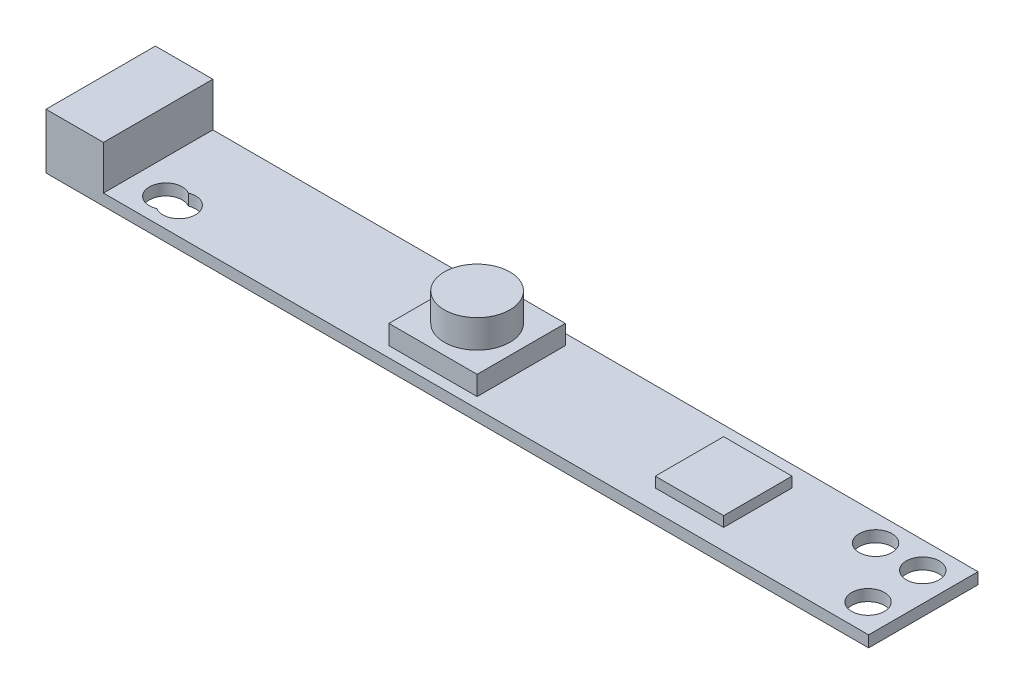
SolidWorks part; units mm, degrees
ref_plane "Front Plane" through (0, 0, 0) normal (0, 0, 1) x (1, 0, 0)
ref_plane "Top Plane" through (0, 0, 0) normal (0, 1, 0) x (1, 0, 0)
ref_plane "Right Plane" through (0, 0, 0) normal (1, 0, 0) x (0, 0, -1)
sketch "Sketch1" plane through (0, 0, 0) normal (0, 1, 0) x (1, 0, 0)
  line L1 (-30.075, -4) -> (30.075, -4)
  line L2 (-30.075, -4) -> (-30.075, 4)
  line L3 (-30.075, 4) -> (30.075, 4)
  line L4 (30.075, -4) -> (30.075, 4)
  line L5 (-30.075, -4) -> (30.075, 4) construction
  line L6 (-30.075, 4) -> (30.075, -4) construction
  point P0 (0, 0)
  dimension "D1" = 60.15
  dimension "D2" = 8
extrude "Boss-Extrude1" add sketch "Sketch1" along normal blind 0.83
sketch "Sketch2" plane through (0, 0.83, 0) normal (0, 1, 0) x (1, 0, 0)
  line L0 (-30.075, 4) -> (-30.075, -4) construction
  line L1 (-5.775, 3.225) -> (0.675, 3.225)
  line L2 (-5.775, 3.225) -> (-5.775, -3.225)
  line L3 (-5.775, -3.225) -> (0.675, -3.225)
  line L4 (0.675, 3.225) -> (0.675, -3.225)
  line L5 (-5.775, 3.225) -> (0.675, -3.225) construction
  line L6 (-5.775, -3.225) -> (0.675, 3.225) construction
  line L7 (30.075, -4) -> (30.075, 4) construction
  circle A0 centre (-2.55, 0) radius 2.4
  point P6 (0, 0)
  dimension "D4" = 4.8
  dimension "D1" = 6.45
  dimension "D2" = 30.75
  dimension "D3" = 35.85
extrude "Boss-Extrude2" add sketch "Sketch2" along normal offset from surface (1.41 mm away) 2.24 contours A0 | L4 L1 L2 L3 A0 region at (-2.55, 0.83, -3.1338) region at (-2.55, 0.83, 0) up to face at (0, 0, 0)
extrude "Boss-Extrude3" add sketch "Sketch2<3>" along normal offset from surface (3.47 mm away) 4.3 contours A0 region at (-2.55, 0.83, 0) up to face at (0, 0, 0)
sketch "Sketch2<3>" plane through (0, 0.83, 0) normal (0, 1, 0) x (1, 0, 0) same geometry as "Sketch2"
sketch "Sketch3" plane through (0, 0.83, 0) normal (0, 1, 0) x (1, 0, 0)
  line L0 (-30.075, -4) -> (30.075, -4) construction
  line L1 (-30.075, 4) -> (-25.875, 4)
  line L2 (-30.075, 4) -> (-30.075, -4)
  line L3 (-30.075, -4) -> (-25.875, -4)
  line L4 (-25.875, 4) -> (-25.875, -4)
  dimension "D1" = 4.2
extrude "Boss-Extrude4" add sketch "Sketch3" along normal offset from surface (3.21 mm away) 4.04 up to face at (0, 0, 0)
hole_wizard "M2 Clearance Hole1" positions "Sketch4" profile "Sketch5" hole size "M2" standard "ISO" end condition up to next
sketch "Sketch4" plane through (0, 0.83, 0) normal (0, 1, 0) x (1, 0, 0)
  line L0 (30.075, -4) -> (30.075, 4) construction
  line L1 (30.075, 4) -> (-25.875, 4) construction
  line L2 (-25.875, -4) -> (30.075, -4) construction
  line L3 (-30.075, -4) -> (-30.075, 4) construction
  point P0 (24.52, 2.065)
  point P2 (27.97, 2.065)
  point P4 (27.97, -1.935)
  point P6 (-23.39, -1.925)
  point P8 (-22.33, -2.005)
  point P11 (0, 0)
  point P12 (0, 0)
  point P19 (0, 0)
  dimension "D1" = 2.105
  dimension "D2" = 1.935
  dimension "D3" = 5.555
  dimension "D4" = 2.065
  dimension "D5" = 1.995
  dimension "D6" = 2.075
  dimension "D7" = 6.685
  dimension "D8" = 52.405
sketch "Sketch5" plane through (24.52, 0.83, -2.065) normal (1, 0, 0) x (0, 0, 1)
  line L0 (0, 0) -> (0, 0.83)
  line L1 (0, 0.83) -> (1.2, 0.83)
  line L2 (1.2, 0.83) -> (1.2, 0)
  line L5 (1.2, 0) -> (0, 0)
  line L11 (0, -6.35) -> (0, 107.95) construction
  dimension "Thru Hole Dia." = 2.4
  dimension "Thru Hole Depth" = 0.83
ref_plane "Plane1" through (-2.55, 0, 0) normal (1, 0, 0) x (0, 0, -1)
sketch "Sketch6" plane through (0, 0.83, 0) normal (0, 1, 0) x (1, 0, 0)
  line L0 (30.075, -4) -> (30.075, 4) construction
  line L1 (12.975, -2.5) -> (17.975, -2.5)
  line L2 (12.975, -2.5) -> (12.975, 2.5)
  line L3 (12.975, 2.5) -> (17.975, 2.5)
  line L4 (17.975, -2.5) -> (17.975, 2.5)
  line L5 (12.975, -2.5) -> (17.975, 2.5) construction
  line L6 (12.975, 2.5) -> (17.975, -2.5) construction
  point P0 (15.475, 0)
  point P7 (0, 0)
  dimension "D1" = 5
  dimension "D2" = 17.1
extrude "Boss-Extrude5" add sketch "Sketch6" along normal offset from surface (0.75 mm away) 1.58 up to face at (24.52, 0, -3.265)
